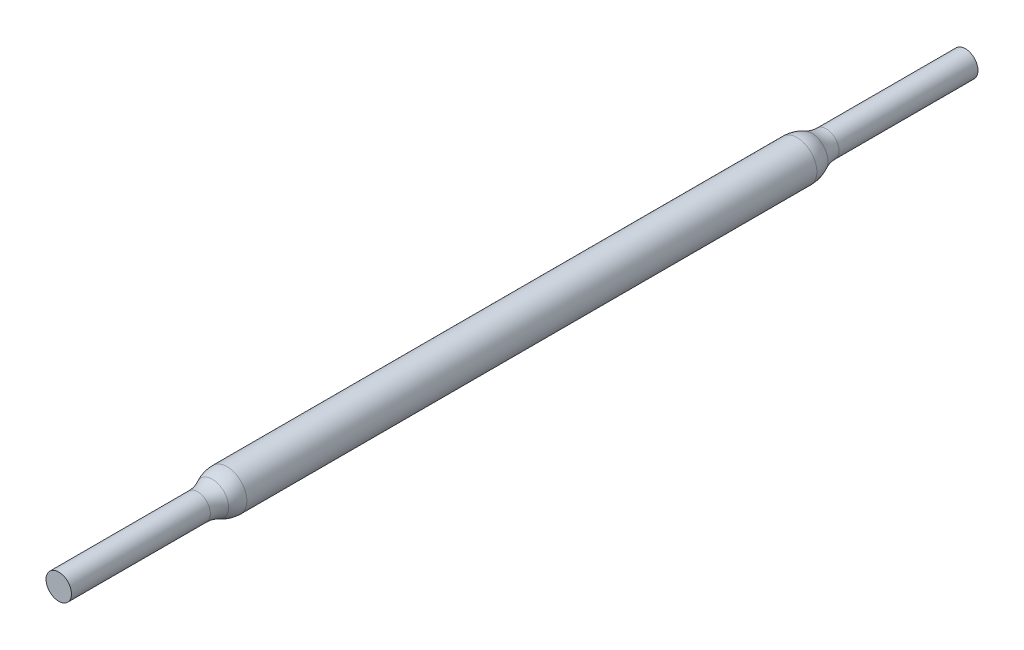
SolidWorks part; units mm, degrees
ref_plane "Front Plane" through (0, 0, 0) normal (0, 0, 1) x (1, 0, 0)
ref_plane "Top Plane" through (0, 0, 0) normal (0, 1, 0) x (1, 0, 0)
ref_plane "Right Plane" through (0, 0, 0) normal (1, 0, 0) x (0, 0, -1)
sketch "Sketch1" plane through (0, 0, 0) normal (0, 0, 1) x (1, 0, 0)
  circle A0 centre (0, 0) radius 4
  dimension "D1" = 8
extrude "Boss-Extrude1" add sketch "Sketch1" along normal blind 50
sketch "Sketch2" plane through (0, 0, 50) normal (0, 0, 1) x (1, 0, 0)
  circle A0 centre (0, 0) radius 6.25
  dimension "D1" = 12.5
extrude "Boss-Extrude2" add sketch "Sketch2" along normal blind 185
sketch "Sketch3" plane through (0, 0, 235) normal (0, 0, 1) x (1, 0, 0)
  circle A0 centre (0, 0) radius 4
  dimension "D1" = 8
extrude "Boss-Extrude3" add sketch "Sketch3" along normal blind 50
fillet "Fillet1" radius 10 2 edges at (4, 0, 50) (4, 0, 235)
fillet "Fillet2" radius 10 2 edges at (6.25, 0, 235) (6.25, 0, 50)
